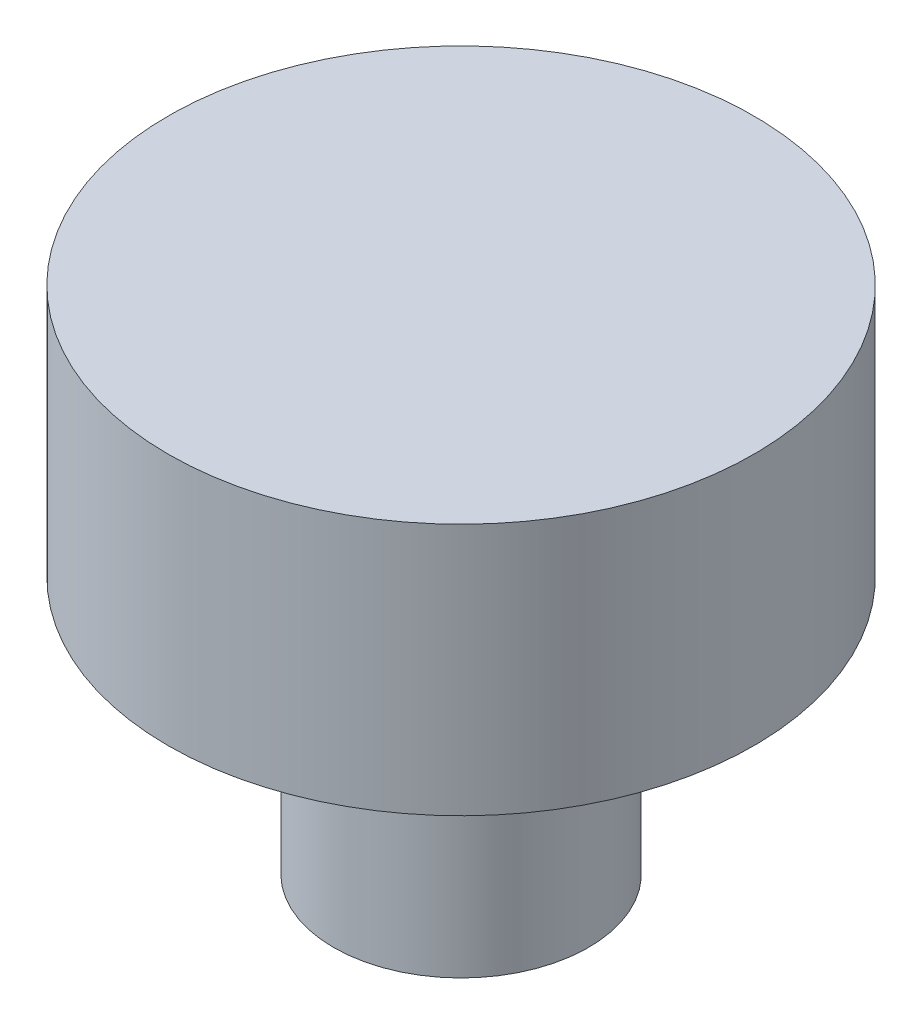
SolidWorks part; units mm, degrees
ref_plane "Front Plane" through (0, 0, 0) normal (0, 0, 1) x (1, 0, 0)
ref_plane "Top Plane" through (0, 0, 0) normal (0, 1, 0) x (1, 0, 0)
ref_plane "Right Plane" through (0, 0, 0) normal (1, 0, 0) x (0, 0, -1)
sketch "Sketch1" plane through (0, 0, 0) normal (0, 1, 0) x (1, 0, 0)
  circle A0 centre (0, 0) radius 5.207
extrude "Boss-Extrude1" add sketch "Sketch1" along normal blind 10.5156
sketch "Sketch2" plane through (0, 10.5156, 0) normal (0, 1, 0) x (1, 0, 0)
  circle A0 centre (0, 0) radius 11.9634
extrude "Boss-Extrude2" add sketch "Sketch2" along normal blind 10.3124 contours A0
